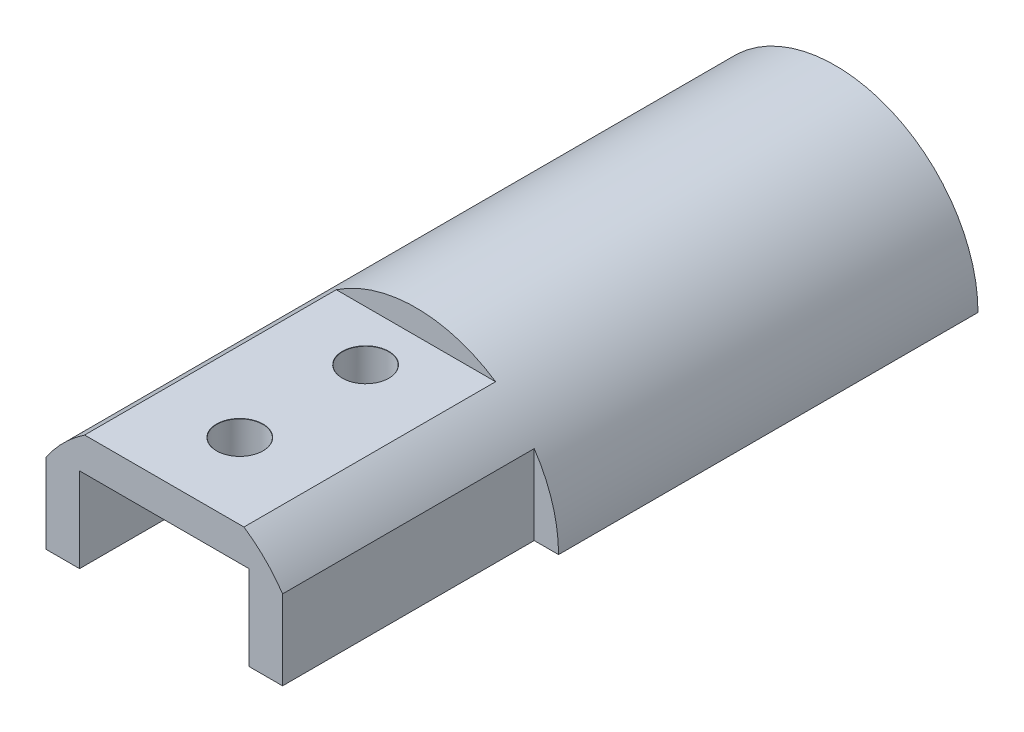
SolidWorks part; units mm, degrees
ref_plane "前视基准面" through (0, 0, 0) normal (0, 0, 1) x (1, 0, 0)
ref_plane "上视基准面" through (0, 0, 0) normal (0, 1, 0) x (1, 0, 0)
ref_plane "右视基准面" through (0, 0, 0) normal (1, 0, 0) x (0, 0, -1)
sketch "草图1" plane through (0, 0, 0) normal (0, 0, 1) x (1, 0, 0)
  circle A0 centre (0, 0) radius 17
  dimension "D1" = 34
extrude "凸台-拉伸1" add sketch "草图1" along normal blind 3
sketch "草图2" plane through (0, 0, 3) normal (0, 0, 1) x (1, 0, 0)
  circle A0 centre (0, 0) radius 17 construction
  circle A1 centre (0, 0) radius 17
  circle A2 centre (0, 0) radius 15
  dimension "D1" = 30
extrude "凸台-拉伸2" add sketch "草图2" along normal blind 40
sketch "草图3" plane through (0, 0, 3) normal (0, 0, 1) x (1, 0, 0)
  circle A0 centre (0, 0) radius 5
  dimension "D1" = 10
extrude "切除-拉伸1" cut sketch "草图3" against normal through all
sketch "草图4" plane through (0, 0, 43) normal (0, 0, 1) x (1, 0, 0)
  line L0 (0, 17) -> (0, -17) construction
  line L1 (-17, 0) -> (0, 0) construction
  line L2 (-4.4431, 10.1) -> (4.4431, 10.1)
  line L7 (10.1, 4.4431) -> (10.1, -4.4431)
  line L8 (-10.1, 4.4431) -> (-10.1, -4.4431)
  line L9 (-4.4431, 10.1) -> (-10.1, 4.4431)
  line L10 (4.4431, 10.1) -> (10.1, 4.4431)
  line L11 (-4.4431, -10.1) -> (-10.1, -4.4431)
  line L12 (-4.4431, -10.1) -> (4.4431, -10.1)
  line L13 (4.4431, -10.1) -> (10.1, -4.4431)
  circle A0 centre (0, 0) radius 17
  point P17 (0, 10.1)
  point P18 (-10.1, 0)
  point P21 (10.1, 0)
  dimension "D1" = 10.1
  dimension "D2" = 10.1
  dimension "D3" = 8
  dimension "D4" = 135
extrude "凸台-拉伸3" add sketch "草图4" along normal blind 7
sketch "草图5" plane through (0, 0, 50) normal (0, 0, 1) x (1, 0, 0)
  line L2 (-9.4968, 14.1) -> (9.4968, 14.1)
  line L4 (-14.1, 9.4968) -> (-14.1, -9.4968)
  line L6 (0, 0) -> (10.1, 10.1) construction
  line L7 (14.1, -9.4968) -> (14.1, 9.4968)
  line L8 (9.4968, -14.1) -> (-9.4968, -14.1)
  line L11 (-10.1, 10.1) -> (-10.1, -10.1)
  line L12 (-10.1, -10.1) -> (10.1, -10.1)
  line L13 (10.1, -10.1) -> (10.1, 10.1)
  line L14 (10.1, 10.1) -> (-10.1, 10.1)
  circle A1 centre (0, 0) radius 17 construction
  arc A2 (-14.1, -9.4968) -> (-9.4968, -14.1) centre (0, 0) ccw
  arc A3 (-9.4968, 14.1) -> (-14.1, 9.4968) centre (0, 0) ccw
  arc A4 (14.1404, 9.4366) -> (9.4366, 14.1404) centre (0, 0) ccw
  arc A5 (14.1, -9.4968) -> (9.4968, -14.1) centre (0, 0) cw
  circle M7 centre (0, 0) radius 17
  dimension "D1" = 4
  dimension "D2" = 4
  dimension "D3" = 20.2
  dimension "D4" = 20.2
extrude "凸台-拉伸4" add sketch "草图5" along normal blind 30 contours L6 A4 L2 L4 M7 | L6 A2 L8 L7 M7 region at (0, 13.7012, 50)
hole_wizard "M5 间隙孔2" positions "草图6" profile "草图7" hole size "M5" standard "ISO" end condition through all
sketch "草图6" plane through (0, 14.1, 0) normal (0, 1, 0) x (1, 0, 0)
  line L2 (-9.4968, -50) -> (9.4968, -50) construction
  line L3 (0, -83) -> (0, -30.4102) construction
  point P0 (0, -56)
  point P2 (0, -71)
  point P22 (0, 0)
  point P23 (0, -74)
  point P24 (0, -74)
  point P25 (0, -67.7187)
  point P26 (0, -73.3564)
  point P27 (0, 0)
  dimension "D1" = 6
  dimension "D2" = 15
sketch "草图7" plane through (0, 14.1, 56) normal (1, 0, 0) x (0, 0, 1)
  line L0 (0, 0) -> (0, 31.1)
  line L1 (0, 31.1) -> (2.75, 31.1)
  line L2 (2.75, 31.1) -> (2.75, 0.025)
  line L3 (2.75, 0.025) -> (2.775, 0)
  line L5 (2.775, 0) -> (0, 0)
  line L6 (-2.75, 0.025) -> (-2.775, 0) construction
  line L11 (0, -6.35) -> (0, 107.95) construction
  dimension "通孔孔直径" = 5.5
  dimension "通孔孔深度" = 31.1
  dimension "近端锥形沉头孔直径" = 5.55
  dimension "近端锥形沉头孔角度" = 90
hole_wizard "M2.5 间隙孔2" positions "草图9" profile "草图10" hole size "M2.5" standard "ISO" end condition through all
sketch "草图9" plane through (0, 0, 3) normal (0, 0, 1) x (1, 0, 0)
  point P0 (11, 0)
  point P11 (11, 0)
  point P12 (11, 0)
  point P13 (11, 0)
  point P20 (11, 0)
  point P21 (11, 0)
  point P22 (11, 0)
  point P31 (7.7782, -7.7782)
  point P32 (0, -11)
  point P33 (-7.7782, -7.7782)
  point P34 (-11, 0)
  point P35 (-7.7782, 7.7782)
  point P36 (0, 11)
  point P37 (7.7782, 7.7782)
  dimension "D1" = 11
  dimension "D2" = 4
  dimension "D3" = 4
  dimension "D4" = 8
sketch "草图10" plane through (11, 0, 3) normal (1, 0, 0) x (0, -1, 0)
  line L0 (0, 0) -> (0, 3)
  line L1 (0, 3) -> (1.45, 3)
  line L2 (1.45, 3) -> (1.45, 0.025)
  line L3 (1.45, 0.025) -> (1.475, 0)
  line L5 (1.475, 0) -> (0, 0)
  line L6 (-1.45, 0.025) -> (-1.475, 0) construction
  line L11 (0, -6.35) -> (0, 107.95) construction
  dimension "通孔孔直径" = 2.9
  dimension "通孔孔深度" = 3
  dimension "近端锥形沉头孔直径" = 2.95
  dimension "近端锥形沉头孔角度" = 90
sketch "草图12" plane through (0, 0, 0) normal (0, 1, 0) x (1, 0, 0)
  line L1 (22.8146, 3.072) -> (-24.3727, 3.072)
  line L2 (22.8146, 3.072) -> (22.8146, -86.2946)
  line L3 (22.8146, -86.2946) -> (-24.3727, -86.2946)
  line L4 (-24.3727, 3.072) -> (-24.3727, -86.2946)
extrude "切除-拉伸2" cut sketch "草图12" against normal blind 18
